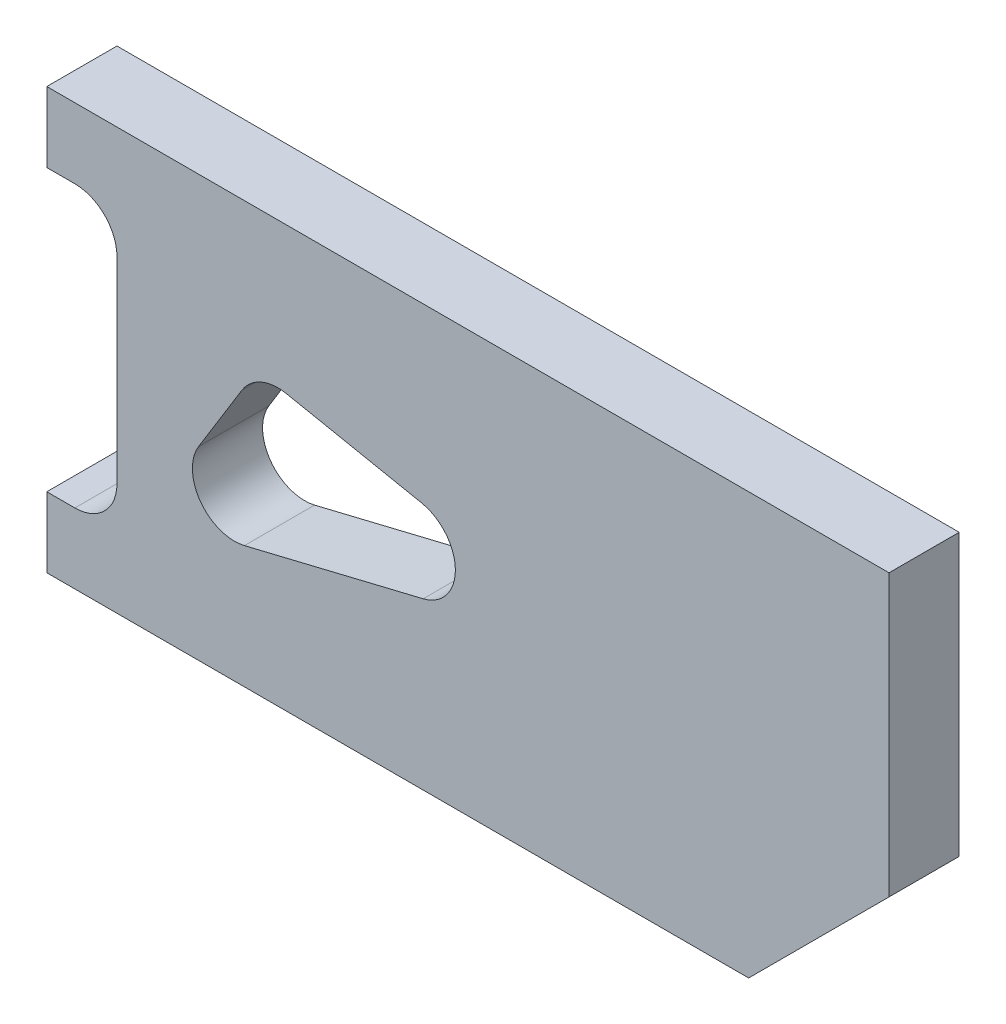
SolidWorks part; units mm, degrees
ref_plane "正面" through (0, 0, 0) normal (0, 0, 1) x (1, 0, 0)
ref_plane "平面" through (0, 0, 0) normal (0, 1, 0) x (1, 0, 0)
ref_plane "右側面" through (0, 0, 0) normal (1, 0, 0) x (0, 0, -1)
sketch "ｽｹｯﾁ1" plane through (0, 0, 0) normal (0, 0, 1) x (1, 0, 0)
  line L1 (0, 0) -> (50, 0)
  line L2 (0, 0) -> (0, 30)
  line L3 (0, 30) -> (60, 30)
  line L4 (60, 10) -> (60, 30)
  line L8 (50, 0) -> (60, 10)
  line L9 (10.8179, 13.2041) -> (13.9051, 18.2209)
  line L10 (17.0485, 19.5903) -> (26.696, 17.6608)
  line L11 (26.8145, 11.8035) -> (14.0797, 8.7163)
  line L13 (0, 25) -> (2, 25)
  line L14 (0, 25) -> (0, 5)
  line L15 (0, 5) -> (2, 5)
  line L16 (5, 22) -> (5, 8)
  arc A0 (14.0797, 8.7163) -> (10.8179, 13.2041) centre (13.3729, 11.6318) cw
  arc A1 (17.0485, 19.5903) -> (13.9051, 18.2209) centre (16.4601, 16.6486) ccw
  arc A2 (26.8145, 11.8035) -> (26.696, 17.6608) centre (26.1077, 14.7191) ccw
  arc A3 (5, 22) -> (2, 25) centre (2, 22) ccw
  arc A4 (2, 5) -> (5, 8) centre (2, 8) ccw
  point P3 (60, 0)
  point P14 (7, 7)
  point P17 (15, 20)
  point P20 (40, 15)
  point P25 (5, 25)
  dimension "D9" = 3
  dimension "D10" = 3
  dimension "D11" = 3
  dimension "D17" = 3
  dimension "D18" = 3
  dimension "Dimension_y" = 10
  dimension "D7" = 10
  dimension "D1" = 7
  dimension "D2" = 15
  dimension "D4" = 40
  dimension "D5" = 7
  dimension "D6" = 20
  dimension "D8" = 15
  dimension "D12" = 60
  dimension "D13" = 30
  dimension "D14" = 5
  dimension "D15" = 5
  dimension "D16" = 5
extrude "ﾎﾞｽ - 押し出し1" add sketch "ｽｹｯﾁ1" along normal blind 5 contours A4 L15 L2 L1 L8 L4 L3 L13 A3 L16 A2 L11 A0 L9 A1 L10 region at (31.8859, 15.4619, 0)
equation "\"A_x\"=7"
equation "\"A_y\"= 7"
equation "\"B_x\"=15"
equation "\"B_y\"=20"
equation "\"C_x\"= 40"
equation "\"C_y\"= 15"
equation "\"Cut_x\"= 10"
equation "\"Cut_y\"= 10"
equation "\"Dimension_y@ｽｹｯﾁ1\" = \"Cut_y\""
equation "\"D7@ｽｹｯﾁ1\"= \"Cut_x\""
equation "\"D2@ｽｹｯﾁ1\"= \"B_x\""
equation "\"D4@ｽｹｯﾁ1\"=\"C_x\""
equation "\"D5@ｽｹｯﾁ1\"=\"A_y\""
equation "\"D6@ｽｹｯﾁ1\"=\"B_y\""
equation "\"D8@ｽｹｯﾁ1\"=\"C_y\""
equation "\"D1@ｽｹｯﾁ1\"= \"A_x\""
